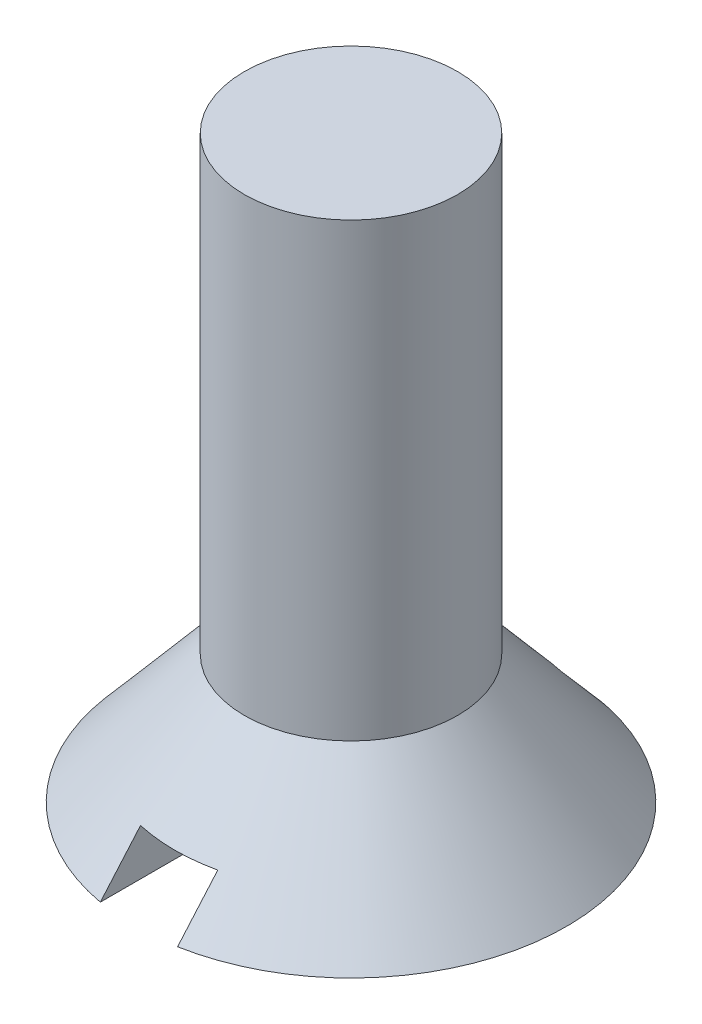
SolidWorks part; units mm, degrees
ref_plane "Front Plane" through (0, 0, 0) normal (0, 0, 1) x (1, 0, 0)
ref_plane "Top Plane" through (0, 0, 0) normal (0, 1, 0) x (1, 0, 0)
ref_plane "Right Plane" through (0, 0, 0) normal (1, 0, 0) x (0, 0, -1)
sketch "Sketch1" plane through (0, 0, 0) normal (0, 1, 0) x (1, 0, 0)
  circle A0 centre (0, 0) radius 3.5433
  dimension "D1" = 7.0866
sketch "Sketch2" plane through (0, 0, 0) normal (0, 0, 1) x (1, 0, 0)
  line L0 (3.5433, 0) -> (-3.5433, 0) construction
  line L1 (3.5433, 0) -> (0, 0)
  line L4 (0, 2.1082) -> (1.7526, 2.1082)
  line L5 (1.7526, 2.1082) -> (3.5433, 0)
  line L6 (0, 2.1082) -> (0, 0)
  dimension "D1" = 2.1082
  dimension "D3" = 1.7526
revolve "Revolve2" add sketch "Sketch2" angle 360 about L6
sketch "Sketch3" plane through (0, 2.1082, 0) normal (0, 1, 0) x (-1, 0, 0)
  circle A0 centre (0, 0) radius 1.7526
extrude "Boss-Extrude1" add sketch "Sketch3" along normal blind 7.4168
sketch "Sketch4" plane through (0, 0, 0) normal (0, 0, 1) x (1, 0, 0)
  line L0 (0, 0) -> (0.635, 0)
  line L1 (3.5433, 0) -> (-3.5433, 0) construction
  line L2 (0.635, 0) -> (0.635, 0.762)
  line L3 (0.635, 0.762) -> (0.1238, 0.762)
  line L4 (0.1238, 0.762) -> (-0.635, 0.762)
  line L5 (-0.635, 0.762) -> (-0.635, 0)
  line L6 (-0.635, 0) -> (0, 0)
  dimension "D1" = 1.27
  dimension "D2" = 0.635
  dimension "D3" = 0.635
  dimension "D4" = 0.762
extrude "Cut-Extrude1" cut sketch "Sketch4" along normal blind 4.1148 and the other way blind 4.572
